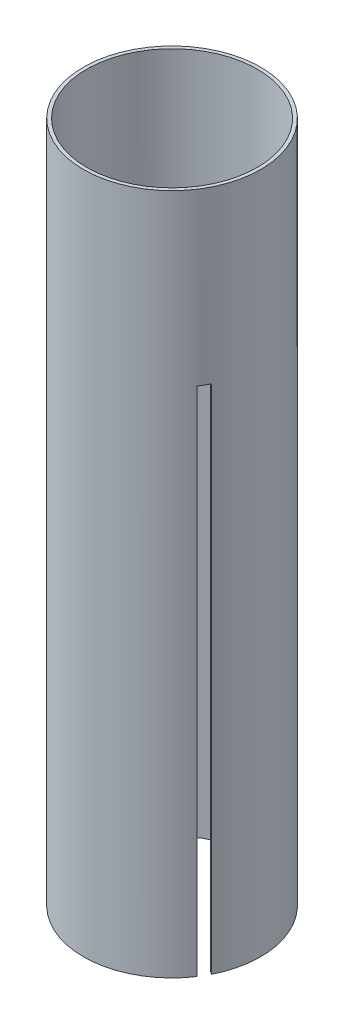
SolidWorks part; units mm, degrees
material "S-Glass Fiber"
ref_plane "Front Plane" through (0, 0, 0) normal (0, 0, 1) x (1, 0, 0)
ref_plane "Top Plane" through (0, 0, 0) normal (0, 1, 0) x (1, 0, 0)
ref_plane "Right Plane" through (0, 0, 0) normal (1, 0, 0) x (0, 0, -1)
sketch "Sketch2" plane through (0, 0, 0) normal (0, 1, 0) x (1, 0, 0)
  circle A0 centre (0, 0) radius 39.624
  circle A1 centre (0, 0) radius 38.1
  dimension "D1" = 79.248
  dimension "D2" = 76.2
extrude "Boss-Extrude1" add sketch "Sketch2" along normal blind 304.8 contours A1 | A0
sketch "Sketch3" plane through (0, 0, 0) normal (0, 0, 1) x (1, 0, 0)
  line L0 (-2.3812, 0) -> (2.3812, 0)
  line L1 (-39.624, 0) -> (39.624, 0) construction
  line L2 (2.3812, 0) -> (2.3812, 228.6)
  line L3 (2.3812, 228.6) -> (-2.3813, 228.6)
  line L4 (-2.3813, 228.6) -> (-2.3812, 0)
  point P6 (0, 0)
  dimension "D1" = 4.7625
  dimension "D2" = 228.6
extrude "Cut-Extrude1" cut sketch "Sketch3" against normal through all
pattern_circular "CirPattern1" count 3 over 360 about axis through (0, 304.8, 0) along (0, -1, 0) of "Cut-Extrude1" reverse direction yes
